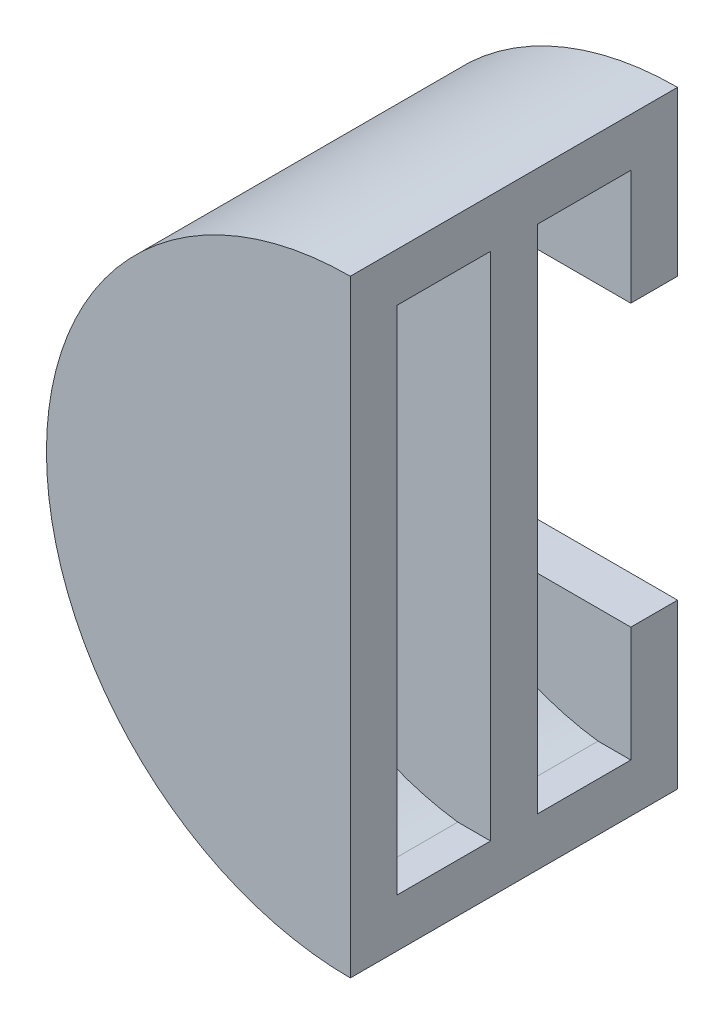
SolidWorks part; units mm, degrees
ref_plane "Front Plane" through (0, 0, 0) normal (0, 0, 1) x (1, 0, 0)
ref_plane "Top Plane" through (0, 0, 0) normal (0, 1, 0) x (1, 0, 0)
ref_plane "Right Plane" through (0, 0, 0) normal (1, 0, 0) x (0, 0, -1)
sketch "Sketch1" plane through (0, 0, 0) normal (0, 0, 1) x (1, 0, 0)
  line L2 (-3.5, 0) -> (-3.5, 32.311)
  line L3 (-3.5, 32.311) -> (-3.5, -32.311)
  arc A0 (-3.5, 32.311) -> (-3.5, -32.311) centre (0, 0) ccw
  dimension "D1" = 65
  dimension "D2" = 3.5
extrude "Boss-Extrude3" add sketch "Sketch1" along normal blind 35 contours L3 A0
sketch "Sketch2" plane through (-3.5, 0, 0) normal (1, 0, 0) x (0, 0, -1)
  line L0 (-20, 27.311) -> (-30, 27.311)
  line L1 (-5, 0) -> (-5, 27.311)
  line L4 (-15, 27.311) -> (-15, -27.311)
  line L7 (-5, -27.311) -> (-5, 0)
  line L9 (-20, -27.311) -> (-20, 27.311)
  line L11 (-30, 27.311) -> (-30, -27.311)
  line L14 (-5, 27.311) -> (-15, 27.311)
  line L15 (-20, -27.311) -> (-30, -27.311)
  line L16 (-15, -27.311) -> (-5, -27.311)
sketch "Sketch4" plane through (0, 0, 0) normal (0, 0, -1) x (-1, 0, 0)
  line L0 (3.5, 0) -> (3.5, 27.311)
  line L1 (3.5, 32.311) -> (3.5, -32.311) construction
  line L4 (3.5, 0) -> (3.5, -27.311)
  line L5 (3.5, -27.311) -> (3.5, 27.311)
  arc A0 (3.5, -27.311) -> (3.5, 27.311) centre (0, 0) ccw
extrude "Cut-Extrude2" cut sketch "Sketch4" against normal blind 10 from offset 5 contours L4 L0 A0 offset against normal yes
extrude "Cut-Extrude3" cut sketch "Sketch4<9>" against normal blind 10 from offset 20 contours A0 L0 L4 offset against normal yes
sketch "Sketch4<9>" plane through (0, 0, 0) normal (0, 0, -1) x (-1, 0, 0) same geometry as "Sketch4"
sketch "Sketch5" plane through (0, 0, 0) normal (0, 0, -1) x (-1, 0, 0)
  circle A0 centre (0, 0) radius 32.5
  dimension "D1" = 65
extrude "Boss-Extrude6" add sketch "Sketch5" along normal mid plane 4 contours A0
sketch "Sketch6" plane through (0, 0, 2) normal (0, 0, 1) x (1, 0, 0)
  line L0 (-3.5, 0) -> (-3.5, 32.311)
  line L1 (-3.5, -32.311) -> (-3.5, 32.311) construction
  line L2 (-3.5, 32.311) -> (-3.5, -32.311)
  arc A0 (-3.5, -32.311) -> (-3.5, 32.311) centre (0, 0) ccw
  dimension "D1" = 65
extrude "Cut-Extrude4" cut sketch "Sketch6" against normal blind 2 contours L2 A0
sketch "Sketch8" plane through (0, 0, -2) normal (0, 0, -1) x (-1, 0, 0)
  circle A0 centre (0, 0) radius 2.5
  dimension "D1" = 5
extrude "Cut-Extrude5" cut sketch "Sketch8" against normal through all contours A0
sketch "Sketch10" plane through (-3.5, 0, 0) normal (1, 0, 0) x (0, 0, -1)
  line L0 (0, 32.311) -> (-35, 32.311)
  line L1 (-35, 32.311) -> (-35, -32.311)
  line L2 (-35, -32.311) -> (0, -32.5)
  line L3 (0, -32.5) -> (0, 32.311)
  line L4 (-5, 27.311) -> (-15, 27.311)
  line L5 (-15, 27.311) -> (-15, -27.311)
  line L6 (-15, -27.311) -> (-5, -27.311)
  line L7 (-5, -27.311) -> (-5, 27.311)
  line L8 (-20, 27.311) -> (-30, 27.311)
  line L9 (-30, 27.311) -> (-30, -27.311)
  line L10 (-30, -27.311) -> (-20, -27.311)
  line L11 (-20, -27.311) -> (-20, 27.311)
sketch "Sketch11" plane through (0, 0, 0) normal (0, 0, 1) x (1, 0, 0)
  circle A0 centre (0, 0) radius 32.5
  dimension "D1" = 65
sketch "Sketch12" plane through (0, 0, 0) normal (0, 0, 1) x (1, 0, 0)
  line L0 (0, 32.5) -> (0, -32.5)
  line L1 (-3.5, -32.311) -> (-3.5, 32.311)
  arc A0 (-3.5, -32.311) -> (0, -32.5) centre (0, 0) ccw
  arc A1 (0, 32.5) -> (-3.5, 32.311) centre (0, 0) ccw
extrude "Boss-Extrude8" add sketch "Sketch12" along normal up to surface (35 mm away) up to face at (-18, 0, 35)
extrude "Cut-Extrude6" cut sketch "Sketch10" along normal blind 11.5 contours L5 L6 L7 L4 | L11 L8 L9 L10
extrude "Cut-Extrude7" cut sketch "Sketch8<4>" against normal blind 10 contours A0
sketch "Sketch8<4>" plane through (0, 0, -2) normal (0, 0, -1) x (-1, 0, 0) same geometry as "Sketch8"
sketch "Sketch13" plane through (0, 0, -2) normal (0, 0, -1) x (-1, 0, 0)
  circle A0 centre (0, 0) radius 35.0169
extrude "Cut-Extrude10" cut sketch "Sketch13" against normal blind 2
sketch "Sketch14" plane through (0, 0, 0) normal (0, 0, -1) x (-1, 0, 0)
  circle A0 centre (0, 0) radius 6
  dimension "D1" = 12
extrude "Cut-Extrude11" cut sketch "Sketch14" against normal blind 8
sketch "Sketch15" plane through (0, 0, 0) normal (0, 0, -1) x (-1, 0, 0)
  line L0 (0, 0) -> (0, 15)
  line L1 (0, 6) -> (0, 32.5) construction
  line L2 (0, 15) -> (22.08, 15)
  line L3 (22.08, 15) -> (22.08, -15)
  line L4 (22.08, -15) -> (0, -15)
  line L5 (0, -32.5) -> (0, -6) construction
  line L6 (0, -15) -> (0, 0)
  dimension "D1" = 15
  dimension "D2" = 22.08
  dimension "D3" = 30
extrude "Cut-Extrude12" cut sketch "Sketch15" against normal blind 8
